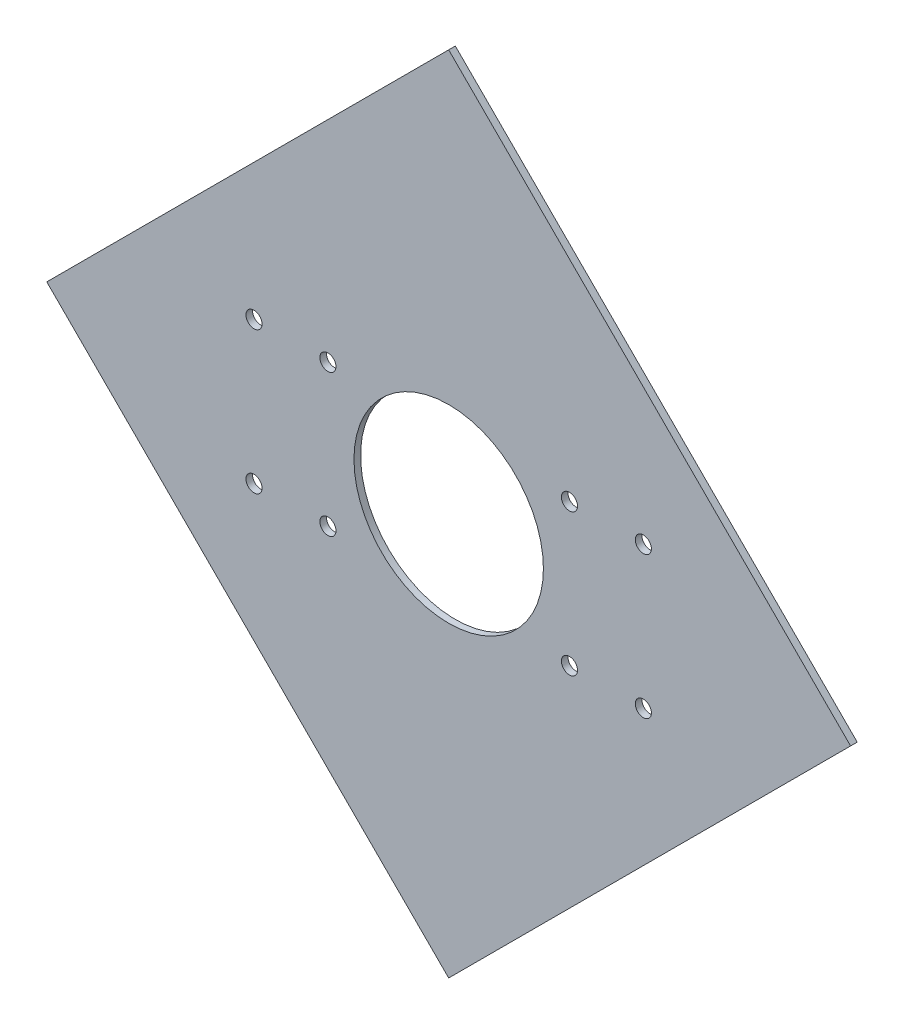
SolidWorks part; units mm, degrees
ref_plane "Front Plane" through (0, 0, 0) normal (0, 0, 1) x (1, 0, 0)
ref_plane "Top Plane" through (0, 0, 0) normal (0, 1, 0) x (1, 0, 0)
ref_plane "Right Plane" through (0, 0, 0) normal (1, 0, 0) x (0, 0, -1)
sketch "Sketch1" plane through (0, 0, 0) normal (0, 0, 1) x (1, 0, 0)
  line L1 (0, 0) -> (84.8528, 84.8528)
  line L2 (0, 0) -> (-84.8528, 84.8528)
  line L3 (-84.8528, 84.8528) -> (0, 169.7056)
  line L4 (84.8528, 84.8528) -> (0, 169.7056)
  point P5 (0, 134.2554)
  point P6 (0, 0)
  point P7 (0, 118.0249)
  point P8 (0, 141.9111)
  dimension "D2" = 120
base flange "Base-Flange1" sketch "Sketch1" thickness 1.4 reverse thickness direction no parameters "D1"=3
sketch "Motor hole" plane through (0, 0, 0) normal (0, 0, 1) x (1, 0, 0)
  circle A0 centre (0, 84.8528) radius 20
  point P2 (0, 0)
  point P3 (0, 0)
  point P4 (0, 0)
  dimension "D1" = 40
extrude "Cut-Extrude1" cut sketch "Motor hole" against normal through all both and the other way through all normal cut yes
sketch "Sketch9" plane through (0, 0, 0) normal (0, 0, 1) x (1, 0, 0)
  line L0 (-41.1, 99.8528) -> (41.1, 99.8528) construction
  line L1 (41.1, 99.8528) -> (41.1, 69.8528) construction
  circle A0 centre (-41.1, 99.8528) radius 1.7
  circle A1 centre (-25.5, 99.8528) radius 1.7
  circle A2 centre (-41.1, 69.8528) radius 1.7
  circle A3 centre (-25.5, 69.8528) radius 1.7
  circle A4 centre (25.5, 99.8528) radius 1.7
  circle A5 centre (41.1, 99.8528) radius 1.7
  circle A6 centre (25.5, 69.8528) radius 1.7
  circle A7 centre (41.1, 69.8528) radius 1.7
  point P16 (0, 99.8528)
  point P17 (41.1, 84.8528)
  point P19 (0, 0)
  point P21 (0, 0)
  point P22 (0, 0)
  point P23 (0, 0)
  point P24 (0, 0)
  point P25 (0, 0)
  dimension "D3" = 3.4
  dimension "D1" = 82.2
  dimension "D2" = 30
  dimension "D4" = 15.6
  dimension "D5" = 15.6
extrude "Cut-Extrude2" cut sketch "Sketch9" against normal through all both and the other way through all normal cut yes
sketch "Bend-Lines1" [suppressed] plane through (0, 0, 0) normal (0, 1, 0) x (1, 0, 0)
sketch "Bounding-Box1" [suppressed] plane through (0, 0, 0) normal (0, 1, 0) x (1, 0, 0)
sheet metal parameters "Sheet-Metal1" thickness 1.4 parameters "D1"=3
flat pattern "Flat-Pattern1" [suppressed]
sketch "Bend-Lines2" plane through (0, 0, 0) normal (0, 1, 0) x (1, 0, 0)
sketch3d "Bounding-Box2" [suppressed]
  line L0 (0, 0, 0) -> (-84.8528, 84.8528, 0) construction
  line L1 (84.8528, 84.8528, 0) -> (0, 169.7056, 0) construction
  line L2 (0, 0, 0) -> (84.8528, 84.8528, 0) construction
  line L3 (-84.8528, 84.8528, 0) -> (0, 169.7056, 0) construction
sheet metal parameters "Sheet-Metal2" thickness 1.4 parameters "D1"=3
flat pattern "Flat-Pattern1"
sketch "Bend-Lines2" plane through (0, 0, 0) normal (0, 1, 0) x (1, 0, 0)
sketch3d "Bounding-Box2" [suppressed]
  line L0 (0, 0, 0) -> (84.8528, 84.8528, 0) construction
  line L1 (-84.8528, 84.8528, 0) -> (0, 169.7056, 0) construction
  line L2 (0, 0, 0) -> (-84.8528, 84.8528, 0) construction
  line L3 (84.8528, 84.8528, 0) -> (0, 169.7056, 0) construction
sheet metal parameters "Sheet-Metal3" thickness 1.4 parameters "D1"=3
flat pattern "Flat-Pattern1"
sketch "Bend-Lines2" plane through (0, 0, 0) normal (0, 1, 0) x (1, 0, 0)
sketch3d "Bounding-Box2" [suppressed]
  line L0 (0, 0, 0) -> (84.8528, 84.8528, 0) construction
  line L1 (-84.8528, 84.8528, 0) -> (0, 169.7056, 0) construction
  line L2 (0, 0, 0) -> (-84.8528, 84.8528, 0) construction
  line L3 (84.8528, 84.8528, 0) -> (0, 169.7056, 0) construction
